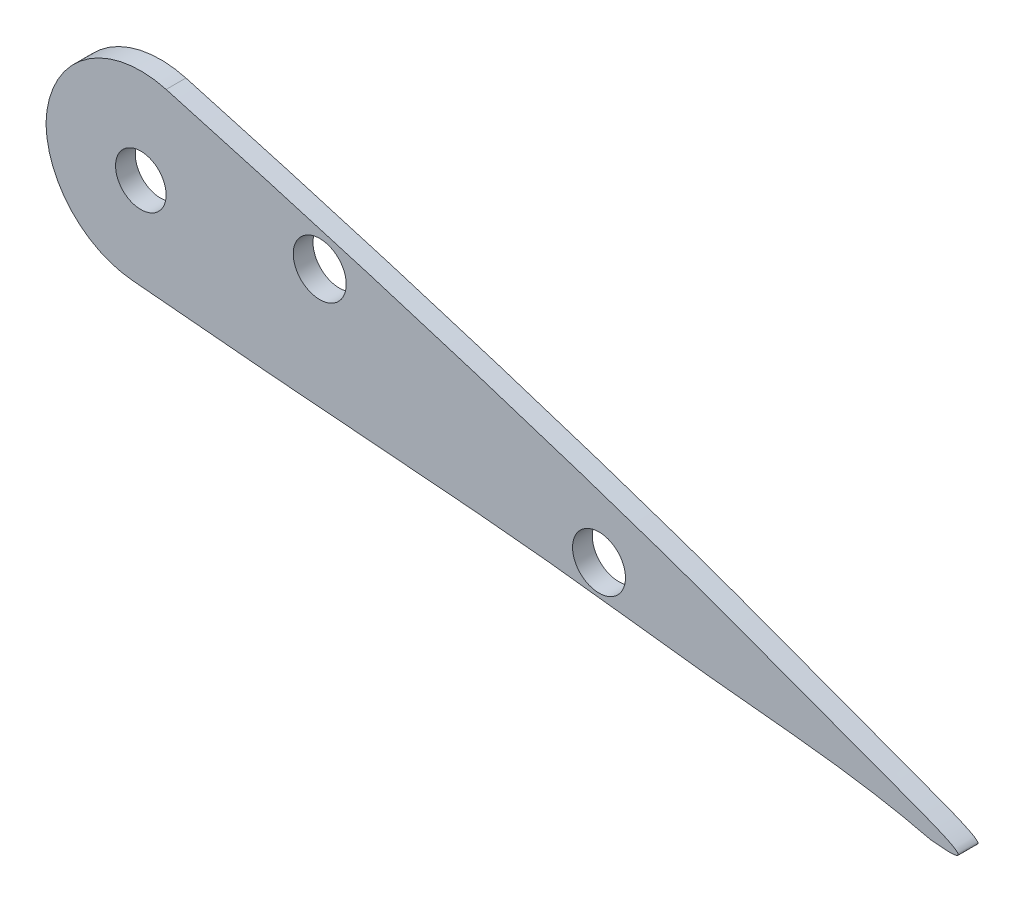
SolidWorks part; units mm, degrees
material "Balsa"
ref_plane "Front Plane" through (0, 0, 0) normal (0, 0, 1) x (1, 0, 0)
ref_plane "Top Plane" through (0, 0, 0) normal (0, 1, 0) x (1, 0, 0)
ref_plane "Right Plane" through (0, 0, 0) normal (1, 0, 0) x (0, 0, -1)
sketch "Sketch1" plane through (0, 0, 0) normal (0, 0, 1) x (1, 0, 0)
  spline S0 degree 3 poles (0.0006, 0.0001) (0.8106, 7.3592) (8.6491, 17.8566) (26.2867, 29.9752) (52.1111, 42.0692) (89.5976, 49.2908) (131.4008, 47.8848) (173.2567, 40.0411) (217.9611, 29.613) (256.9521, 19.5289) (290.3598, 8.711) (301.2732, 4.3828) (314.8169, -0.5162) (309.8463, 0.0001) knots 0 0 0 0 0.060864 0.113688 0.188609 0.312909 0.448482 0.557612 0.691544 0.852438 0.929756 0.976058 1 1 1 1
  spline S1 degree 3 poles (309.8463, 0.0001) (303.9568, 1.471) (293.9895, 2.094) (276.264, 4.5144) (260.8463, 5.4274) (235.8588, 7.8703) (205.1014, 8.8381) (157.7186, 9.0307) (110.4973, 6.1815) (66.5062, -0.5867) (36.4547, -6.0985) (15.3166, -6.1891) (1.2307, -6.9241) (0.0006, 0.0001) knots 0 0 0 0 0.057787 0.095275 0.171021 0.205339 0.335319 0.464904 0.658702 0.785512 0.893517 0.943092 1 1 1 1
extrude "Boss-Extrude1" add sketch "Sketch1" along normal blind 1.5875
sketch "Sketch2" plane through (0, 0, 1.5875) normal (0, 0, 1) x (1, 0, 0)
  circle A0 centre (20.32, 10.16) radius 6.35
  circle A1 centre (227.2963, 19.0501) radius 3.175
  dimension "D2" = 12.7
  dimension "D3" = 6.35
  dimension "D6" = 20.32
  dimension "D1" = 82.55
  dimension "D4" = 19.05
  dimension "D5" = 10.16
extrude "Cut-Extrude1" cut sketch "Sketch2" against normal through all
sketch "Sketch3" plane through (0, 0, 1.5875) normal (0, 0, 1) x (1, 0, 0)
  line L11 (-90.3395, -69.7561) -> (238.7263, -69.7561)
  line L12 (-90.3395, -69.7561) -> (-90.3395, 107.5465)
  line L13 (-90.3395, 107.5465) -> (238.7263, 107.5465)
  line L14 (238.7263, -69.7561) -> (238.7263, 107.5465)
  circle A1 centre (227.2963, 19.0501) radius 3.175 construction
  dimension "D1" = 11.43
extrude "Cut-Extrude2" cut sketch "Sketch3" against normal through all contours L14 L13 L12 L11
fillet "Fillet1" radius 7.62 2 edges at (238.7263, 7.3795, 0.7937) (238.7263, 24.1211, 0.7937)
sketch "Sketch4" plane through (0, 0, 1.5875) normal (0, 0, 1) x (1, 0, 0)
  circle A0 centre (246.3463, 14.163) radius 2.032
  dimension "D1" = 4.064
  dimension "D2" = 63.5
  dimension "D3" = 14.1628
extrude "Cut-Extrude3" cut sketch "Sketch4" against normal blind 2.54
sketch "Sketch5" plane through (0, 0, 1.5875) normal (0, 0, 1) x (1, 0, 0)
  circle A0 centre (260.7202, 15.1782) radius 2.127
  circle A1 centre (283.1572, 5.9778) radius 2.127
  point P4 (283.1572, 5.9778)
  point P5 (260.7202, 15.1782)
  dimension "D1" = 4.254
extrude "Cut-Extrude4" cut sketch "Sketch5" against normal blind 2.54
equation "\"D1@Sketch3\"=0.25+0.2"
